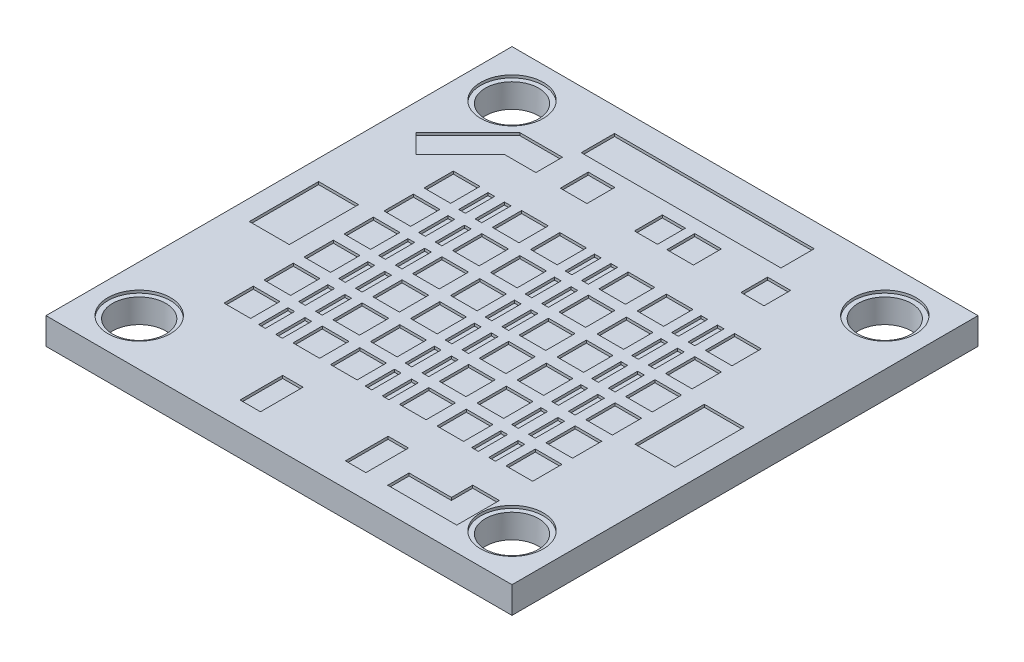
SolidWorks part; units mm, degrees
note: The reader was unsure of these and kept them because the rebuilt part matched: thickness of "Base-Flange2".
ref_plane "Front Plane" through (0, 0, 0) normal (0, 0, 1) x (1, 0, 0)
ref_plane "Top Plane" through (0, 0, 0) normal (0, 1, 0) x (1, 0, 0)
ref_plane "Right Plane" through (0, 0, 0) normal (1, 0, 0) x (0, 0, -1)
sketch "Sketch1" plane through (0, 0, 0) normal (0, 1, 0) x (1, 0, 0)
  line L0 (0, 17.5) -> (0, 14.3923) construction
  line L1 (17.5, 17.5) -> (-17.5, 17.5)
  line L2 (17.5, 17.5) -> (17.5, -17.5)
  line L3 (17.5, -17.5) -> (-17.5, -17.5)
  line L4 (-17.5, 17.5) -> (-17.5, -17.5)
  line L5 (17.5, 17.5) -> (-17.5, -17.5) construction
  line L6 (17.5, -17.5) -> (-17.5, 17.5) construction
  line L7 (17.5, 0) -> (1.35, 0) construction
  line L9 (-14, -17.5) -> (-14, -14) construction
  line L10 (-14, -14) -> (14, -14) construction
  circle A2 centre (-14, -14) radius 2
  circle A3 centre (14, -14) radius 2
  circle A4 centre (14, 14) radius 2
  circle A5 centre (-14, 14) radius 2
  point P0 (0, 0)
  dimension "D3" = 4
  dimension "D4" = 3.5
  dimension "D1" = 35
  dimension "D2" = 35
base flange "Base-Flange2" sketch "Sketch1" thickness 2 reverse thickness direction no parameters "D1"=0.7366
sketch "Sketch2" plane through (0, 0, 0) normal (0, 1, 0) x (1, 0, 0)
  line L0 (0, 0) -> (0, 1.1728) construction
  line L1 (0, 0) -> (0.8707, 0) construction
  line L2 (14, 14) -> (8.8938, 14) construction
  line L3 (14, 14) -> (14, 9.8363) construction
  line L4 (12, 14) -> (12, 13.1533)
  line L5 (-8, 15.7) -> (7, 15.7)
  line L6 (-8, 15.7) -> (-8, 13.2)
  line L7 (-8, 13.2) -> (7, 13.2)
  line L8 (7, 15.7) -> (7, 13.2)
  line L9 (-8, 15.7) -> (7, 13.2) construction
  line L10 (-8, 13.2) -> (7, 15.7) construction
  line L11 (-6.4758, 12.2) -> (-4.4758, 12.2)
  line L12 (-7.6077, 12.2) -> (-7.6077, 10.2)
  line L13 (-6.4758, 10.1037) -> (-4.4758, 10.1037)
  line L17 (-13, 12.2679) -> (-13, 12.5489)
  line L18 (-13, 12.2679) -> (-10.2154, 12.2679) construction
  line L19 (-11.6077, 12.2679) -> (-11.6077, 7.2) construction
  line L20 (-3.6077, 7.2) -> (-3.6077, 5)
  line L21 (-11.6077, 7.2) -> (-9.6077, 7.2)
  line L22 (-11.6077, 7.2) -> (-11.6077, 5)
  line L23 (-11.6077, 5) -> (-9.6077, 5)
  line L24 (-9.6077, 7.2) -> (-9.6077, 5)
  line L25 (-8.9077, 7.1037) -> (-8.4077, 7.1037)
  line L26 (-8.9077, 7.1037) -> (-8.9077, 4.9037)
  line L27 (-8.9077, 4.9037) -> (-8.4077, 4.9037)
  line L28 (-8.4077, 7.1037) -> (-8.4077, 4.9037)
  line L29 (-3.6077, 7.2) -> (-1.6077, 7.2)
  line L30 (-1.6077, 7.2) -> (-1.6077, 5)
  line L31 (-3.6077, 5) -> (-1.6077, 5)
  line L32 (-0.9077, 7.1037) -> (-0.9077, 4.9037)
  line L33 (-0.9077, 7.1037) -> (-0.4077, 7.1037)
  line L34 (-0.4077, 7.1037) -> (-0.4077, 4.9037)
  line L35 (-0.9077, 4.9037) -> (-0.4077, 4.9037)
  line L36 (4.3923, 7.2) -> (4.3923, 5)
  line L37 (4.3923, 7.2) -> (6.3923, 7.2)
  line L38 (6.3923, 7.2) -> (6.3923, 5)
  line L39 (4.3923, 5) -> (6.3923, 5)
  line L40 (7.0923, 7.1037) -> (7.0923, 4.9037)
  line L41 (7.0923, 7.1037) -> (7.5923, 7.1037)
  line L42 (7.5923, 7.1037) -> (7.5923, 4.9037)
  line L43 (7.0923, 4.9037) -> (7.5923, 4.9037)
  line L44 (-3.6128, 4.2) -> (-3.6128, 2)
  line L45 (-3.6128, 4.2) -> (-1.6128, 4.2)
  line L46 (-1.6128, 4.2) -> (-1.6128, 2)
  line L47 (-3.6128, 2) -> (-1.6128, 2)
  line L48 (-0.9128, 4.1037) -> (-0.9128, 1.9037)
  line L49 (-0.9128, 4.1037) -> (-0.4128, 4.1037)
  line L50 (-0.4128, 4.1037) -> (-0.4128, 1.9037)
  line L51 (-0.9128, 1.9037) -> (-0.4128, 1.9037)
  line L52 (4.3872, 4.2) -> (4.3872, 2)
  line L53 (4.3872, 4.2) -> (6.3872, 4.2)
  line L54 (6.3872, 4.2) -> (6.3872, 2)
  line L55 (4.3872, 2) -> (6.3872, 2)
  line L56 (7.0872, 4.1037) -> (7.0872, 1.9037)
  line L57 (7.0872, 4.1037) -> (7.5872, 4.1037)
  line L58 (7.5872, 4.1037) -> (7.5872, 1.9037)
  line L59 (7.0872, 1.9037) -> (7.5872, 1.9037)
  line L60 (-3.618, 1.2) -> (-3.618, -1)
  line L61 (-3.618, 1.2) -> (-1.618, 1.2)
  line L62 (-1.618, 1.2) -> (-1.618, -1)
  line L63 (-3.618, -1) -> (-1.618, -1)
  line L64 (-0.918, 1.1037) -> (-0.918, -1.0963)
  line L65 (-0.918, 1.1037) -> (-0.418, 1.1037)
  line L66 (-0.418, 1.1037) -> (-0.418, -1.0963)
  line L67 (-0.918, -1.0963) -> (-0.418, -1.0963)
  line L68 (4.382, 1.2) -> (4.382, -1)
  line L69 (4.382, 1.2) -> (6.382, 1.2)
  line L70 (6.382, 1.2) -> (6.382, -1)
  line L71 (4.382, -1) -> (6.382, -1)
  line L72 (7.082, 1.1037) -> (7.082, -1.0963)
  line L73 (7.082, 1.1037) -> (7.582, 1.1037)
  line L74 (7.582, 1.1037) -> (7.582, -1.0963)
  line L75 (7.082, -1.0963) -> (7.582, -1.0963)
  line L76 (-3.6231, -1.8) -> (-3.6231, -4)
  line L77 (-3.6231, -1.8) -> (-1.6231, -1.8)
  line L78 (-1.6231, -1.8) -> (-1.6231, -4)
  line L79 (-3.6231, -4) -> (-1.6231, -4)
  line L80 (-0.9231, -1.8963) -> (-0.9231, -4.0963)
  line L81 (-0.9231, -1.8963) -> (-0.4231, -1.8963)
  line L82 (-0.4231, -1.8963) -> (-0.4231, -4.0963)
  line L83 (-0.9231, -4.0963) -> (-0.4231, -4.0963)
  line L84 (4.3769, -1.8) -> (4.3769, -4)
  line L85 (4.3769, -1.8) -> (6.3769, -1.8)
  line L86 (6.3769, -1.8) -> (6.3769, -4)
  line L87 (4.3769, -4) -> (6.3769, -4)
  line L88 (7.0769, -1.8963) -> (7.0769, -4.0963)
  line L89 (7.0769, -1.8963) -> (7.5769, -1.8963)
  line L90 (7.5769, -1.8963) -> (7.5769, -4.0963)
  line L91 (7.0769, -4.0963) -> (7.5769, -4.0963)
  line L92 (-3.6283, -4.8) -> (-3.6283, -7)
  line L93 (-3.6283, -4.8) -> (-1.6283, -4.8)
  line L94 (-1.6283, -4.8) -> (-1.6283, -7)
  line L95 (-3.6283, -7) -> (-1.6283, -7)
  line L96 (-0.9283, -4.8963) -> (-0.9283, -7.0963)
  line L97 (-0.9283, -4.8963) -> (-0.4283, -4.8963)
  line L98 (-0.4283, -4.8963) -> (-0.4283, -7.0963)
  line L99 (-0.9283, -7.0963) -> (-0.4283, -7.0963)
  line L100 (4.3717, -4.8) -> (4.3717, -7)
  line L101 (4.3717, -4.8) -> (6.3717, -4.8)
  line L102 (6.3717, -4.8) -> (6.3717, -7)
  line L103 (4.3717, -7) -> (6.3717, -7)
  line L104 (7.0717, -4.8963) -> (7.0717, -7.0963)
  line L105 (7.0717, -4.8963) -> (7.5717, -4.8963)
  line L106 (7.5717, -4.8963) -> (7.5717, -7.0963)
  line L107 (7.0717, -7.0963) -> (7.5717, -7.0963)
  line L108 (-3.6334, -7.8) -> (-3.6334, -10)
  line L109 (-3.6334, -7.8) -> (-1.6334, -7.8)
  line L110 (-1.6334, -7.8) -> (-1.6334, -10)
  line L111 (-3.6334, -10) -> (-1.6334, -10)
  line L112 (-0.9334, -7.8963) -> (-0.9334, -10.0963)
  line L113 (-0.9334, -7.8963) -> (-0.4334, -7.8963)
  line L114 (-0.4334, -7.8963) -> (-0.4334, -10.0963)
  line L115 (-0.9334, -10.0963) -> (-0.4334, -10.0963)
  line L116 (4.3666, -7.8) -> (4.3666, -10)
  line L117 (4.3666, -7.8) -> (6.3666, -7.8)
  line L118 (6.3666, -7.8) -> (6.3666, -10)
  line L119 (4.3666, -10) -> (6.3666, -10)
  line L120 (7.0666, -7.8963) -> (7.0666, -10.0963)
  line L121 (7.0666, -7.8963) -> (7.5666, -7.8963)
  line L122 (7.5666, -7.8963) -> (7.5666, -10.0963)
  line L123 (7.0666, -10.0963) -> (7.5666, -10.0963)
  line L140 (-11.6128, 4.2) -> (-11.6128, 2)
  line L141 (-11.6128, 4.2) -> (-9.6128, 4.2)
  line L142 (-9.6128, 4.2) -> (-9.6128, 2)
  line L143 (-11.6128, 2) -> (-9.6128, 2)
  line L144 (-8.9128, 4.1037) -> (-8.9128, 1.9037)
  line L145 (-8.9128, 4.1037) -> (-8.4128, 4.1037)
  line L146 (-8.4128, 4.1037) -> (-8.4128, 1.9037)
  line L147 (-8.9128, 1.9037) -> (-8.4128, 1.9037)
  line L148 (-11.618, 1.2) -> (-11.618, -1)
  line L149 (-11.618, 1.2) -> (-9.618, 1.2)
  line L150 (-9.618, 1.2) -> (-9.618, -1)
  line L151 (-11.618, -1) -> (-9.618, -1)
  line L152 (-8.918, 1.1037) -> (-8.918, -1.0963)
  line L153 (-8.918, 1.1037) -> (-8.418, 1.1037)
  line L154 (-8.418, 1.1037) -> (-8.418, -1.0963)
  line L155 (-8.918, -1.0963) -> (-8.418, -1.0963)
  line L156 (-11.6231, -1.8) -> (-11.6231, -4)
  line L157 (-11.6231, -1.8) -> (-9.6231, -1.8)
  line L158 (-9.6231, -1.8) -> (-9.6231, -4)
  line L159 (-11.6231, -4) -> (-9.6231, -4)
  line L160 (-8.9231, -1.8963) -> (-8.9231, -4.0963)
  line L161 (-8.9231, -1.8963) -> (-8.4231, -1.8963)
  line L162 (-8.4231, -1.8963) -> (-8.4231, -4.0963)
  line L163 (-8.9231, -4.0963) -> (-8.4231, -4.0963)
  line L164 (-11.6283, -4.8) -> (-11.6283, -7)
  line L165 (-11.6283, -4.8) -> (-9.6283, -4.8)
  line L166 (-9.6283, -4.8) -> (-9.6283, -7)
  line L167 (-11.6283, -7) -> (-9.6283, -7)
  line L168 (-8.9283, -4.8963) -> (-8.9283, -7.0963)
  line L169 (-8.9283, -4.8963) -> (-8.4283, -4.8963)
  line L170 (-8.4283, -4.8963) -> (-8.4283, -7.0963)
  line L171 (-8.9283, -7.0963) -> (-8.4283, -7.0963)
  line L172 (-11.6334, -7.8) -> (-11.6334, -10)
  line L173 (-11.6334, -7.8) -> (-9.6334, -7.8)
  line L174 (-9.6334, -7.8) -> (-9.6334, -10)
  line L175 (-11.6334, -10) -> (-9.6334, -10)
  line L176 (-8.9334, -7.8963) -> (-8.9334, -10.0963)
  line L177 (-8.9334, -7.8963) -> (-8.4334, -7.8963)
  line L178 (-8.4334, -7.8963) -> (-8.4334, -10.0963)
  line L179 (-8.9334, -10.0963) -> (-8.4334, -10.0963)
  line L191 (-8.0417, 4.9235) -> (-8.0417, 5.313) construction
  line L197 (-7.1501, -7.8963) -> (-7.6501, -7.8963)
  line L198 (-7.6501, -7.8963) -> (-7.6501, -10.0963)
  line L199 (-7.1501, -10.0963) -> (-7.6501, -10.0963)
  line L200 (-7.1501, -7.8963) -> (-7.1501, -10.0963)
  line L201 (-4.4501, -7.8) -> (-6.4501, -7.8)
  line L202 (-6.4501, -7.8) -> (-6.4501, -10)
  line L203 (-4.4501, -10) -> (-6.4501, -10)
  line L204 (-4.4501, -7.8) -> (-4.4501, -10)
  line L205 (-7.1552, -4.8963) -> (-7.6552, -4.8963)
  line L206 (-7.6552, -4.8963) -> (-7.6552, -7.0963)
  line L207 (-7.1552, -7.0963) -> (-7.6552, -7.0963)
  line L208 (-7.1552, -4.8963) -> (-7.1552, -7.0963)
  line L209 (-4.4552, -4.8) -> (-6.4552, -4.8)
  line L210 (-6.4552, -4.8) -> (-6.4552, -7)
  line L211 (-4.4552, -7) -> (-6.4552, -7)
  line L212 (-4.4552, -4.8) -> (-4.4552, -7)
  line L213 (-7.1604, -1.8963) -> (-7.6604, -1.8963)
  line L214 (-7.6604, -1.8963) -> (-7.6604, -4.0963)
  line L215 (-7.1604, -4.0963) -> (-7.6604, -4.0963)
  line L216 (-7.1604, -1.8963) -> (-7.1604, -4.0963)
  line L217 (-4.4604, -1.8) -> (-6.4604, -1.8)
  line L218 (-6.4604, -1.8) -> (-6.4604, -4)
  line L219 (-4.4604, -4) -> (-6.4604, -4)
  line L220 (-4.4604, -1.8) -> (-4.4604, -4)
  line L221 (-7.1655, 1.1037) -> (-7.6655, 1.1037)
  line L222 (-7.6655, 1.1037) -> (-7.6655, -1.0963)
  line L223 (-7.1655, -1.0963) -> (-7.6655, -1.0963)
  line L224 (-7.1655, 1.1037) -> (-7.1655, -1.0963)
  line L225 (-4.4655, 1.2) -> (-6.4655, 1.2)
  line L226 (-6.4655, 1.2) -> (-6.4655, -1)
  line L227 (-4.4655, -1) -> (-6.4655, -1)
  line L228 (-4.4655, 1.2) -> (-4.4655, -1)
  line L229 (-7.1706, 4.1037) -> (-7.6706, 4.1037)
  line L230 (-7.6706, 4.1037) -> (-7.6706, 1.9037)
  line L231 (-7.1706, 1.9037) -> (-7.6706, 1.9037)
  line L232 (-7.1706, 4.1037) -> (-7.1706, 1.9037)
  line L233 (-4.4706, 4.2) -> (-6.4706, 4.2)
  line L234 (-6.4706, 4.2) -> (-6.4706, 2)
  line L235 (-4.4706, 2) -> (-6.4706, 2)
  line L236 (-4.4706, 4.2) -> (-4.4706, 2)
  line L237 (-7.1758, 4.9037) -> (-7.6758, 4.9037)
  line L238 (-7.6758, 7.1037) -> (-7.6758, 4.9037)
  line L239 (-7.1758, 7.1037) -> (-7.6758, 7.1037)
  line L240 (-7.1758, 7.1037) -> (-7.1758, 4.9037)
  line L241 (-4.4758, 5) -> (-6.4758, 5)
  line L242 (-6.4758, 7.2) -> (-6.4758, 5)
  line L243 (-4.4758, 7.2) -> (-6.4758, 7.2)
  line L244 (-4.4758, 7.2) -> (-4.4758, 5)
  line L245 (3.5242, 5) -> (1.5242, 5)
  line L246 (1.5242, 7.2) -> (1.5242, 5)
  line L247 (3.5242, 7.2) -> (1.5242, 7.2)
  line L248 (3.5242, 7.2) -> (3.5242, 5)
  line L249 (0.8242, 4.9037) -> (0.3242, 4.9037)
  line L250 (0.3242, 7.1037) -> (0.3242, 4.9037)
  line L251 (0.8242, 7.1037) -> (0.3242, 7.1037)
  line L252 (0.8242, 7.1037) -> (0.8242, 4.9037)
  line L253 (3.5294, 4.2) -> (1.5294, 4.2)
  line L254 (1.5294, 4.2) -> (1.5294, 2)
  line L255 (3.5294, 2) -> (1.5294, 2)
  line L256 (3.5294, 4.2) -> (3.5294, 2)
  line L257 (0.8294, 4.1037) -> (0.3294, 4.1037)
  line L258 (0.3294, 4.1037) -> (0.3294, 1.9037)
  line L259 (0.8294, 1.9037) -> (0.3294, 1.9037)
  line L260 (0.8294, 4.1037) -> (0.8294, 1.9037)
  line L261 (3.5345, 1.2) -> (1.5345, 1.2)
  line L262 (1.5345, 1.2) -> (1.5345, -1)
  line L263 (3.5345, -1) -> (1.5345, -1)
  line L264 (3.5345, 1.2) -> (3.5345, -1)
  line L265 (0.8345, 1.1037) -> (0.3345, 1.1037)
  line L266 (0.3345, 1.1037) -> (0.3345, -1.0963)
  line L267 (0.8345, -1.0963) -> (0.3345, -1.0963)
  line L268 (0.8345, 1.1037) -> (0.8345, -1.0963)
  line L269 (3.5396, -1.8) -> (1.5396, -1.8)
  line L270 (1.5396, -1.8) -> (1.5396, -4)
  line L271 (3.5396, -4) -> (1.5396, -4)
  line L272 (3.5396, -1.8) -> (3.5396, -4)
  line L273 (0.8396, -1.8963) -> (0.3396, -1.8963)
  line L274 (0.3396, -1.8963) -> (0.3396, -4.0963)
  line L275 (0.8396, -4.0963) -> (0.3396, -4.0963)
  line L276 (0.8396, -1.8963) -> (0.8396, -4.0963)
  line L277 (3.5448, -4.8) -> (1.5448, -4.8)
  line L278 (1.5448, -4.8) -> (1.5448, -7)
  line L279 (3.5448, -7) -> (1.5448, -7)
  line L280 (3.5448, -4.8) -> (3.5448, -7)
  line L281 (0.8448, -4.8963) -> (0.3448, -4.8963)
  line L282 (0.3448, -4.8963) -> (0.3448, -7.0963)
  line L283 (0.8448, -7.0963) -> (0.3448, -7.0963)
  line L284 (0.8448, -4.8963) -> (0.8448, -7.0963)
  line L285 (3.5499, -7.8) -> (1.5499, -7.8)
  line L286 (1.5499, -7.8) -> (1.5499, -10)
  line L287 (3.5499, -10) -> (1.5499, -10)
  line L288 (3.5499, -7.8) -> (3.5499, -10)
  line L289 (0.8499, -7.8963) -> (0.3499, -7.8963)
  line L290 (0.3499, -7.8963) -> (0.3499, -10.0963)
  line L291 (0.8499, -10.0963) -> (0.3499, -10.0963)
  line L292 (0.8499, -7.8963) -> (0.8499, -10.0963)
  line L301 (11.5242, 5) -> (9.5242, 5)
  line L302 (9.5242, 7.2) -> (9.5242, 5)
  line L303 (11.5242, 7.2) -> (9.5242, 7.2)
  line L304 (11.5242, 7.2) -> (11.5242, 5)
  line L305 (8.8242, 4.9037) -> (8.3242, 4.9037)
  line L306 (8.3242, 7.1037) -> (8.3242, 4.9037)
  line L307 (8.8242, 7.1037) -> (8.3242, 7.1037)
  line L308 (8.8242, 7.1037) -> (8.8242, 4.9037)
  line L309 (11.5294, 4.2) -> (9.5294, 4.2)
  line L310 (9.5294, 4.2) -> (9.5294, 2)
  line L311 (11.5294, 2) -> (9.5294, 2)
  line L312 (11.5294, 4.2) -> (11.5294, 2)
  line L313 (8.8294, 4.1037) -> (8.3294, 4.1037)
  line L314 (8.3294, 4.1037) -> (8.3294, 1.9037)
  line L315 (8.8294, 1.9037) -> (8.3294, 1.9037)
  line L316 (8.8294, 4.1037) -> (8.8294, 1.9037)
  line L317 (11.5345, 1.2) -> (9.5345, 1.2)
  line L318 (9.5345, 1.2) -> (9.5345, -1)
  line L319 (11.5345, -1) -> (9.5345, -1)
  line L320 (11.5345, 1.2) -> (11.5345, -1)
  line L321 (8.8345, 1.1037) -> (8.3345, 1.1037)
  line L322 (8.3345, 1.1037) -> (8.3345, -1.0963)
  line L323 (8.8345, -1.0963) -> (8.3345, -1.0963)
  line L324 (8.8345, 1.1037) -> (8.8345, -1.0963)
  line L325 (11.5396, -1.8) -> (9.5396, -1.8)
  line L326 (9.5396, -1.8) -> (9.5396, -4)
  line L327 (11.5396, -4) -> (9.5396, -4)
  line L328 (11.5396, -1.8) -> (11.5396, -4)
  line L329 (8.8396, -1.8963) -> (8.3396, -1.8963)
  line L330 (8.3396, -1.8963) -> (8.3396, -4.0963)
  line L331 (8.8396, -4.0963) -> (8.3396, -4.0963)
  line L332 (8.8396, -1.8963) -> (8.8396, -4.0963)
  line L333 (11.5448, -4.8) -> (9.5448, -4.8)
  line L334 (9.5448, -4.8) -> (9.5448, -7)
  line L335 (11.5448, -7) -> (9.5448, -7)
  line L336 (11.5448, -4.8) -> (11.5448, -7)
  line L337 (8.8448, -4.8963) -> (8.3448, -4.8963)
  line L338 (8.3448, -4.8963) -> (8.3448, -7.0963)
  line L339 (8.8448, -7.0963) -> (8.3448, -7.0963)
  line L340 (8.8448, -4.8963) -> (8.8448, -7.0963)
  line L341 (11.5499, -7.8) -> (9.5499, -7.8)
  line L342 (9.5499, -7.8) -> (9.5499, -10)
  line L343 (11.5499, -10) -> (9.5499, -10)
  line L344 (11.5499, -7.8) -> (11.5499, -10)
  line L345 (8.8499, -7.8963) -> (8.3499, -7.8963)
  line L346 (8.3499, -7.8963) -> (8.3499, -10.0963)
  line L347 (8.8499, -10.0963) -> (8.3499, -10.0963)
  line L348 (8.8499, -7.8963) -> (8.8499, -10.0963)
  line L357 (-3.6385, -10.8) -> (-3.6385, -13) [skipped]
  line L358 (-3.6385, -10.8) -> (-1.6385, -10.8) [skipped]
  line L359 (-1.6385, -10.8) -> (-1.6385, -13) [skipped]
  line L360 (-3.6385, -13) -> (-1.6385, -13) [skipped]
  line L361 (-0.9385, -10.8963) -> (-0.9385, -13.0963) [skipped]
  line L362 (-0.9385, -10.8963) -> (-0.4385, -10.8963) [skipped]
  line L363 (-0.4385, -10.8963) -> (-0.4385, -13.0963) [skipped]
  line L364 (-0.9385, -13.0963) -> (-0.4385, -13.0963) [skipped]
  line L365 (4.3615, -10.8) -> (4.3615, -13) [skipped]
  line L366 (4.3615, -10.8) -> (6.3615, -10.8) [skipped]
  line L367 (6.3615, -10.8) -> (6.3615, -13) [skipped]
  line L368 (4.3615, -13) -> (6.3615, -13) [skipped]
  line L369 (7.0615, -10.8963) -> (7.0615, -13.0963) [skipped]
  line L370 (7.0615, -10.8963) -> (7.5615, -10.8963) [skipped]
  line L371 (7.5615, -10.8963) -> (7.5615, -13.0963) [skipped]
  line L372 (7.0615, -13.0963) -> (7.5615, -13.0963) [skipped]
  line L373 (-11.6385, -10.8) -> (-11.6385, -13) [skipped]
  line L374 (-11.6385, -10.8) -> (-9.6385, -10.8) [skipped]
  line L375 (-9.6385, -10.8) -> (-9.6385, -13) [skipped]
  line L376 (-11.6385, -13) -> (-9.6385, -13) [skipped]
  line L377 (-8.9385, -10.8963) -> (-8.9385, -13.0963) [skipped]
  line L378 (-8.9385, -10.8963) -> (-8.4385, -10.8963) [skipped]
  line L379 (-8.4385, -10.8963) -> (-8.4385, -13.0963) [skipped]
  line L380 (-8.9385, -13.0963) -> (-8.4385, -13.0963) [skipped]
  line L381 (0, -17.5) -> (0, -16.1079) construction
  line L382 (-17.5, -17.5) -> (17.5, -17.5) construction
  line L387 (-12.9842, 1.4574) -> (-15.9842, 1.4574)
  line L388 (12.9842, -3.7426) -> (15.9842, -3.7426)
  line L389 (12.9842, -3.7426) -> (12.9842, 1.4574)
  line L390 (12.9842, 1.4574) -> (15.9842, 1.4574)
  line L391 (15.9842, -3.7426) -> (15.9842, 1.4574)
  line L392 (12.9842, -3.7426) -> (15.9842, 1.4574) construction
  line L393 (12.9842, 1.4574) -> (15.9842, -3.7426) construction
  line L394 (-15.9842, -3.7426) -> (-15.9842, 1.4574)
  line L395 (-12.9842, -3.7426) -> (-15.9842, -3.7426)
  line L396 (-12.9842, -3.7426) -> (-12.9842, 1.4574)
  line L397 (14, -14) -> (11.5499, -14) construction
  line L398 (11.5499, -14) -> (14, -14) construction
  line L399 (14, -14) -> (14, -11.5387) construction
  line L400 (4.3666, -10) -> (3.5499, -10) construction
  line L401 (3.9583, -10) -> (3.9583, -10.5244) construction
  line L402 (-4.7253, -15.7) -> (-3.1912, -15.7)
  line L403 (4.7253, -12.5) -> (3.1912, -12.5)
  line L404 (4.7253, -12.5) -> (4.7253, -15.7)
  line L405 (4.7253, -15.7) -> (3.1912, -15.7)
  line L406 (3.1912, -12.5) -> (3.1912, -15.7)
  line L407 (4.7253, -12.5) -> (3.1912, -15.7) construction
  line L408 (4.7253, -15.7) -> (3.1912, -12.5) construction
  line L409 (-3.1912, -12.5) -> (-3.1912, -15.7)
  line L410 (-4.7253, -12.5) -> (-3.1912, -12.5)
  line L411 (-4.7253, -12.5) -> (-4.7253, -15.7)
  line L412 (-6.4758, 10.1037) -> (-6.4758, 12.2)
  line L413 (-4.4758, 10.1037) -> (-4.4758, 12.2)
  line L414 (-0.9077, 10.1037) -> (-0.9077, 12.2)
  line L415 (0.8242, 10.1037) -> (0.8242, 12.2)
  line L416 (1.5242, 10.1037) -> (1.5242, 12.2)
  line L417 (3.5242, 10.1037) -> (3.5242, 12.2)
  line L418 (-0.9077, 12.2) -> (0.8242, 12.2)
  line L421 (-0.9077, 10.1037) -> (0.8242, 10.1037)
  line L422 (1.5242, 12.2) -> (3.5242, 12.2)
  line L425 (1.5242, 10.1037) -> (3.5242, 10.1037)
  line L426 (-17.5, 0) -> (-16.5615, 0) construction
  line L427 (6.3666, -14.1) -> (9.5499, -14.1)
  line L428 (6.3666, -14.1) -> (6.3666, -15.7)
  line L429 (6.3666, -15.7) -> (11.5499, -15.7)
  line L430 (11.5499, -14.1) -> (11.5499, -15.7)
  line L431 (9.5499, -12.5) -> (11.5499, -12.5)
  line L432 (9.5499, -12.5) -> (9.5499, -14.1)
  line L434 (11.5499, -12.5) -> (11.5499, -14.1)
  line L435 (7.0923, 10.1037) -> (8.8242, 10.1037)
  line L436 (7.0923, 10.1037) -> (7.0923, 12.1037)
  line L437 (7.0923, 12.1037) -> (8.8242, 12.1037)
  line L438 (8.8242, 10.1037) -> (8.8242, 12.1037)
  line L439 (-8.4077, 10.2) -> (-10.7792, 10.2)
  line L440 (-8.4077, 10.2) -> (-8.4077, 12.2)
  line L441 (-8.4077, 12.2) -> (-11.6077, 12.2)
  line L443 (-17.5, 17.5) -> (-17.5, -17.5) construction
  line L444 (17.5, 17.5) -> (-17.5, 17.5) construction
  line L445 (17.5, -17.5) -> (17.5, 17.5) construction
  line L446 (-11.6077, 12.2) -> (-15.5142, 8.2935)
  line L447 (-10.7792, 10.2) -> (-14.1, 6.8793)
  line L448 (-14.1, 6.8793) -> (-15.5142, 8.2935)
  circle A0 centre (14, 14) radius 2 construction
  circle A1 centre (-14, 14) radius 2 construction
  circle A2 centre (-14, 14) radius 2.35
  circle A3 centre (-14, -14) radius 2.35
  circle A4 centre (14, -14) radius 2.35
  circle A5 centre (14, 14) radius 2.35
  point P7 (-0.5, 14.45)
  point P13 (-0.1077, 11.1037)
  point P36 (14.4842, -1.1426)
  point P141 (-14.4842, -1.1426)
  point P191 (3.9583, -14.1)
  point P196 (-3.9583, -14.1)
  point P263 (-10.6077, 7.2)
  point P312 (10.5499, -12.5)
  point P313 (7.3166, -10.0963)
  point P440 (-14, -14)
  point P443 (14, -14)
  point P444 (14, 14)
  point P456 (-14.4842, 14.45)
  point P457 (0, 0)
  point P458 (-14.0008, -14.0324)
  dimension "D1" = 5
  dimension "D5" = 1.8
  dimension "D45" = 3.5
  dimension "D46" = 4.7
  dimension "D47" = 3.5
  dimension "D2" = 5
  dimension "D3" = 2.5
  dimension "D4" = 15
  dimension "D6" = 2
  dimension "D7" = 1
  dimension "D8" = 4
  dimension "D9" = 6
  dimension "D10" = 2
  dimension "D11" = 2.2
  dimension "D12" = 2.2
  dimension "D13" = 0.5
  dimension "D14" = 0.7
  dimension "D15" = 3
  dimension "D17" = 0.3659
  dimension "D18" = 1.7319
  dimension "D19" = 3
  dimension "D20" = 3.2
  dimension "D21" = 1.5341
  dimension "D22" = 1.8
  dimension "D23" = 1.7319
  dimension "D24" = 2
  dimension "D25" = 1.0963
  dimension "D26" = 3
  dimension "D27" = 2.9037
  dimension "D28" = 3.5681
  dimension "D29" = 8.6758
  dimension "D30" = 3.5681
  dimension "D31" = 2
  dimension "D32" = 3
  dimension "D33" = 3
  dimension "D34" = 5.2
  dimension "D35" = 1.5158
  dimension "D36" = 2.5
  dimension "D37" = 4.0037
  dimension "D38" = 1.8
  dimension "D39" = 2
  dimension "D40" = 3.1833
  dimension "D41" = 1.6
  dimension "D42" = 1.6413
  dimension "D43" = 6.3824
  dimension "D44" = 5.8872
  dimension "D48" = 10.2574
  dimension "D49" = 135
  dimension "D50" = 1.9319
  dimension "D51" = 5.1058
  dimension "D52" = 28
  dimension "D16" = 7
extrude "Cut-Extrude1" cut sketch "Sketch2" against normal blind 0.2
sketch "Bend-Lines3" [suppressed] plane through (0, 0, 0) normal (0, 1, 0) x (1, 0, 0)
sketch "Bounding-Box3" [suppressed] plane through (0, 0, 0) normal (0, 1, 0) x (1, 0, 0)
sheet metal parameters "Sheet-Metal2" thickness 2 parameters "D1"=0.7366
flat pattern "Flat-Pattern2" [suppressed]
sketch "Bend-Lines4" plane through (0, 0, 0) normal (0, 1, 0) x (1, 0, 0)
sketch3d "Bounding-Box4" [suppressed]
  line L0 (17.5, 17.5, 0) -> (-17.5, 17.5, 0) construction
  line L1 (17.5, -17.5, 0) -> (-17.5, -17.5, 0) construction
  line L2 (17.5, 17.5, 0) -> (17.5, -17.5, 0) construction
  line L3 (-17.5, 17.5, 0) -> (-17.5, -17.5, 0) construction
sheet metal parameters "Sheet-Metal7" thickness 2 parameters "D1"=0.7366, "D7"=0.2
flat pattern "Flat-Pattern2"
sketch "Bend-Lines4" plane through (0, 0, 0) normal (0, 1, 0) x (1, 0, 0)
sketch3d "Bounding-Box4" [suppressed]
  line L0 (-17.5, 17.5, 0) -> (17.5, 17.5, 0) construction
  line L1 (-17.5, -17.5, 0) -> (17.5, -17.5, 0) construction
  line L2 (-17.5, 17.5, 0) -> (-17.5, -17.5, 0) construction
  line L3 (17.5, 17.5, 0) -> (17.5, -17.5, 0) construction
